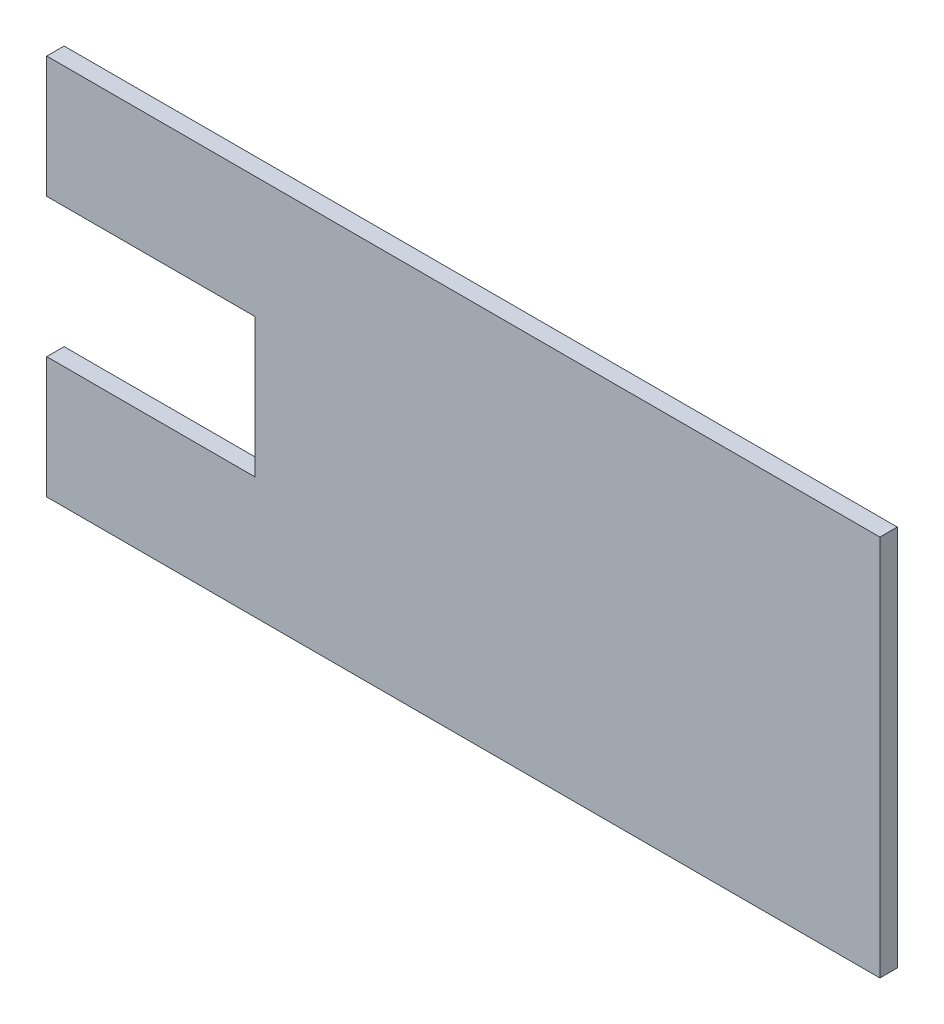
SolidWorks part; units mm, degrees
ref_plane "Front Plane" through (0, 0, 0) normal (0, 0, 1) x (1, 0, 0)
ref_plane "Top Plane" through (0, 0, 0) normal (0, 1, 0) x (1, 0, 0)
ref_plane "Right Plane" through (0, 0, 0) normal (1, 0, 0) x (0, 0, -1)
sketch "Sketch1" plane through (0, 0, 0) normal (0, 0, 1) x (1, 0, 0)
  line L1 (0, 0) -> (152.4, 0)
  line L2 (0, 0) -> (0, 69.85)
  line L3 (0, 69.85) -> (152.4, 69.85)
  line L4 (152.4, 0) -> (152.4, 69.85)
  dimension "D1" = 69.85
  dimension "D2" = 152.4
extrude "Boss-Extrude1" add sketch "Sketch1" along normal blind 3.175
sketch "Sketch2" plane through (0, 0, 3.175) normal (0, 0, 1) x (1, 0, 0)
  line L0 (0, 69.85) -> (0, 0) construction
  line L1 (0, 47.625) -> (38.1, 47.625)
  line L2 (0, 47.625) -> (0, 22.225)
  line L3 (0, 22.225) -> (38.1, 22.225)
  line L4 (38.1, 47.625) -> (38.1, 22.225)
  line L5 (152.4, 0) -> (152.4, 69.85) construction
  point P6 (38.1, 34.925)
  point P7 (152.4, 34.925)
  dimension "D1" = 25.4
  dimension "D2" = 38.1
extrude "Cut-Extrude1" cut sketch "Sketch2" against normal through all
